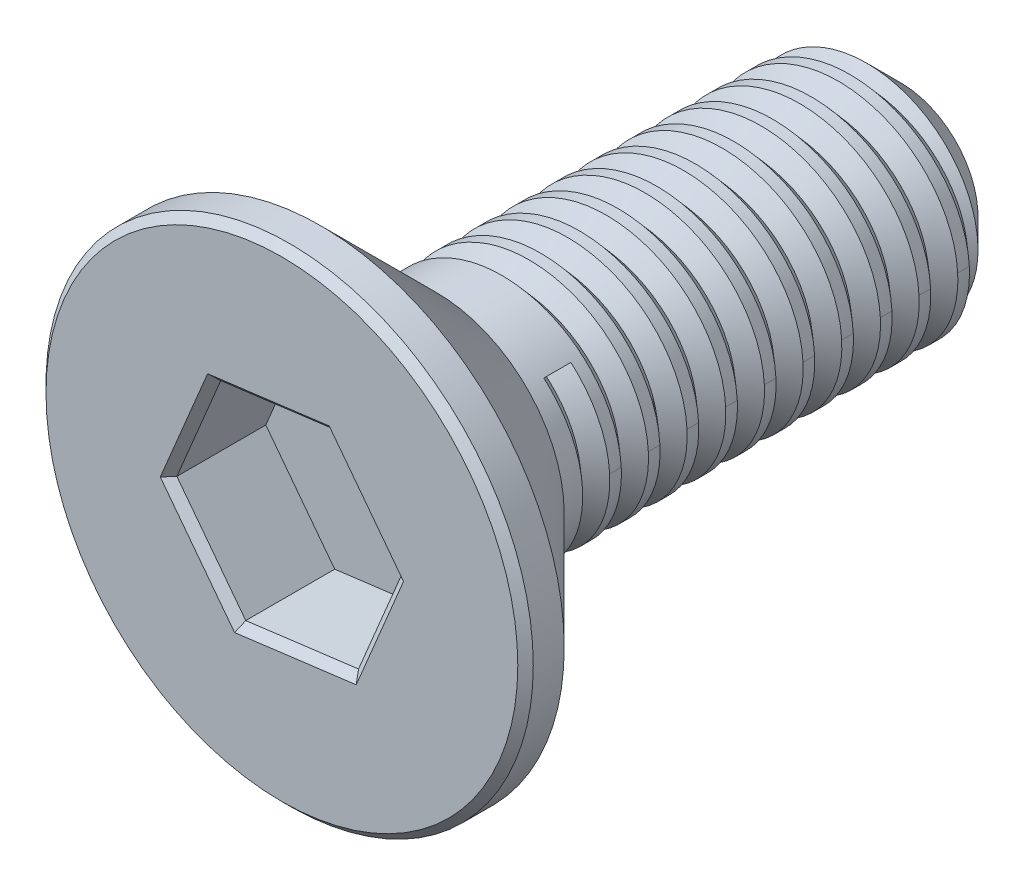
SolidWorks part; units mm, degrees
ref_plane "前视基准面" through (0, 0, 0) normal (0, 0, 1) x (1, 0, 0)
ref_plane "上视基准面" through (0, 0, 0) normal (0, 1, 0) x (1, 0, 0)
ref_plane "右视基准面" through (0, 0, 0) normal (1, 0, 0) x (0, 0, -1)
sketch "草图1" plane through (0, 0, 0) normal (0, 0, 1) x (1, 0, 0)
  circle A0 centre (0, 0) radius 6.3
  dimension "D1" = 12.6
extrude "凸台-拉伸1" add sketch "草图1" along normal blind 1
sketch "草图2" plane through (0, 0, 0) normal (0, 1, 0) x (1, 0, 0)
  line L0 (0, 0) -> (0, 3)
  line L1 (0, 3) -> (-3.3, 3)
  line L2 (-3.3, 3) -> (-6.3, 0)
  line L3 (-6.3, 0) -> (0, 0)
  dimension "D1" = 3
  dimension "D2" = 3.3
revolve "旋转2" add sketch "草图2" angle 360 about L0
sketch "草图3" plane through (0, 0, -3) normal (0, 0, -1) x (-1, 0, 0)
  circle A0 centre (0, 0) radius 3
  dimension "D1" = 6
extrude "凸台-拉伸2" add sketch "草图3" along normal blind 12
sketch "草图4" plane through (0, 0, 1) normal (0, 0, 1) x (1, 0, 0)
  line L1 (1.1343, 2.712) -> (-1.7815, 2.3383)
  line L2 (-1.7815, 2.3383) -> (-2.9158, -0.3737)
  line L3 (-2.9158, -0.3737) -> (-1.1343, -2.712)
  line L4 (-1.1343, -2.712) -> (1.7815, -2.3383)
  line L5 (1.7815, -2.3383) -> (2.9158, 0.3737)
  line L6 (2.9158, 0.3737) -> (1.1343, 2.712)
  circle A0 centre (0, 0) radius 2.5458 construction
extrude "切除-拉伸1" cut sketch "草图4" against normal blind 2.5
chamfer "倒角1" distance 1 angle 45 1 edges at (-3, 0, -15)
sketch "草图5" plane through (0, 0, -15) normal (0, 0, -1) x (-1, 0, 0)
  circle A0 centre (0, 0) radius 3
curve "螺旋线/涡状线1" pitch 1 height 11 radius 3 centre (0, 0, -15) axis (0, 0, 1) start towards (0.7071, 0.7071, 0)
sketch "草图6" plane through (0, 0, 0) normal (1, 0, 0) x (0, 0, -1)
  line L0 (14.525, 3) -> (15.225, 3)
  line L1 (14.875, 3) -> (14.875, 2.6) construction
  line L2 (14.525, 3) -> (14.875, 2.6)
  line L3 (14.875, 2.6) -> (15.225, 3)
  dimension "D1" = 0.7
  dimension "D2" = 0.4
sweep "切除-扫描1" cut profiles "草图6" path "螺旋线/涡状线1"
chamfer "倒角2" distance 0.2 angle 45 7 edges at (6.3, 0, 1) (-0.3236, 2.5251, 1) (-2.3486, 0.9823, 1) (-2.025, -1.5428, 1) (0.3236, -2.5251, 1) (2.3486, -0.9823, 1) (2.025, 1.5428, 1)
